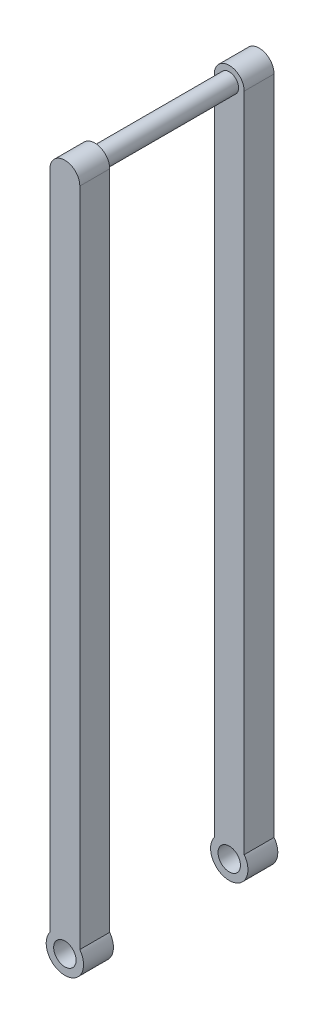
SolidWorks part; units mm, degrees
ref_plane "Front Plane" through (0, 0, 0) normal (0, 0, 1) x (1, 0, 0)
ref_plane "Top Plane" through (0, 0, 0) normal (0, 1, 0) x (1, 0, 0)
ref_plane "Right Plane" through (0, 0, 0) normal (1, 0, 0) x (0, 0, -1)
sketch "Sketch1" plane through (0, 0, 0) normal (0, 0, 1) x (1, 0, 0)
  line L0 (2, 0) -> (2, 90) construction
  line L1 (-2, 0) -> (-2, 90) construction
  line L2 (-2, 90) -> (-2, 1.5)
  line L3 (2, 90) -> (2, 1.5)
  circle A0 centre (0, 0) radius 1.5
  circle A1 centre (0, 0) radius 2.5 construction
  circle A2 centre (0, 0) radius 2 construction
  arc A4 (-2, 90) -> (2, 90) centre (0, 90) cw
  arc A5 (2, 1.5) -> (-2, 1.5) centre (0, 0) cw
  circle A7 centre (0, 90) radius 1.25
  point P10 (-2, 90)
  dimension "D1" = 3
  dimension "D2" = 1
  dimension "D3" = 4
  dimension "D6" = 2.5
  dimension "D4" = 90
  dimension "D5" = 90
extrude "Boss-Extrude1" add sketch "Sketch1" along normal blind 2 and the other way blind 2 contours A7 | A5 L3 A4 L2 A7 A0 region at (0, 44.6924, 0) region at (0, 90, 0)
ref_plane "Plane1" through (0, 0, 11) normal (0, 0, 1) x (1, 0, 0)
mirror "Mirror2" about plane through (0, 0, 11) normal (0, 0, 1) of bodies 101
extrude "Boss-Extrude2" add sketch "Sketch1<4>" along normal up to surface (20 mm away) contours A7 up to face at (0, 45.25, 20)
sketch "Sketch1<4>" plane through (0, 0, 0) normal (0, 0, 1) x (1, 0, 0) same geometry as "Sketch1"
